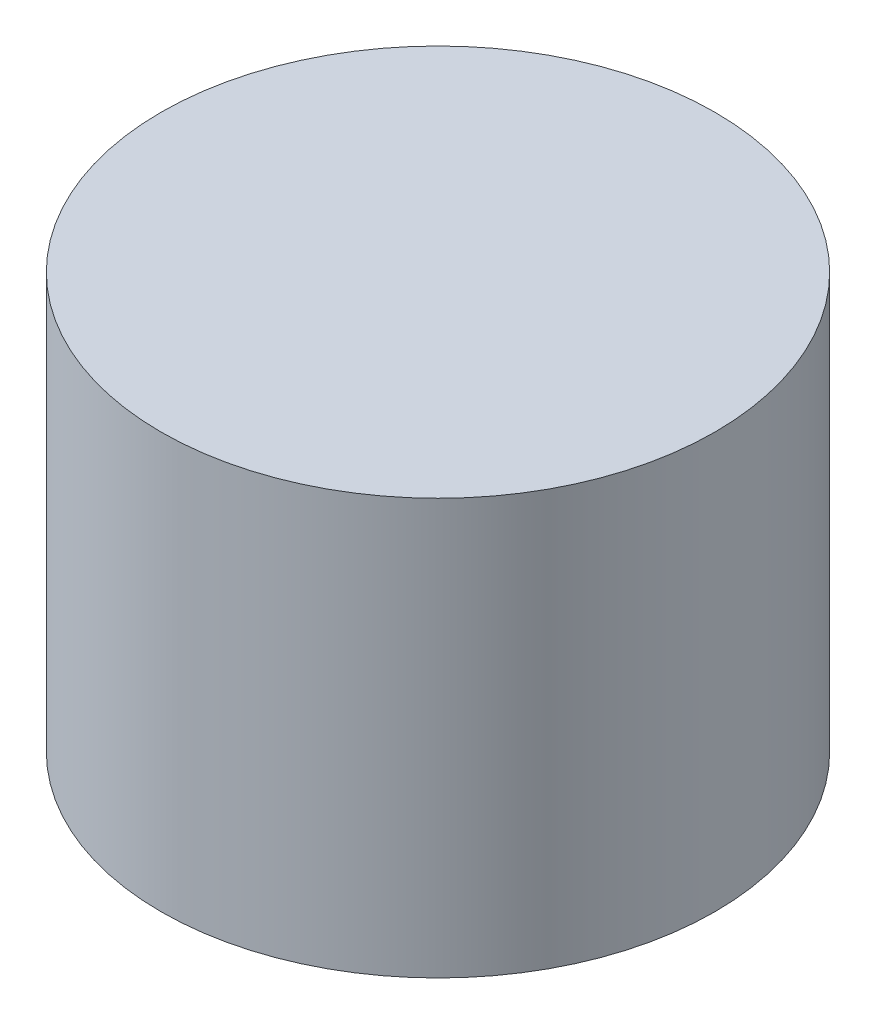
SolidWorks part; units mm, degrees
note: '?' marks a value the reader was unsure of.
ref_plane "Front Plane" through (0, 0, 0) normal (0, 0, 1) x (1, 0, 0)
ref_plane "Top Plane" through (0, 0, 0) normal (0, 1, 0) x (1, 0, 0)
ref_plane "Right Plane" through (0, 0, 0) normal (1, 0, 0) x (0, 0, -1)
ref_axis "Axis1" through (0, 0, 0) along (0, 1, 0)?
sketch "Sketch1" plane through (0, 0, 0) normal (0, 1, 0) x (1, 0, 0)
  circle A0 centre (0, 0) radius 2
  dimension "D1" = 4
extrude "Boss-Extrude1" add sketch "Sketch1" along normal blind 3
